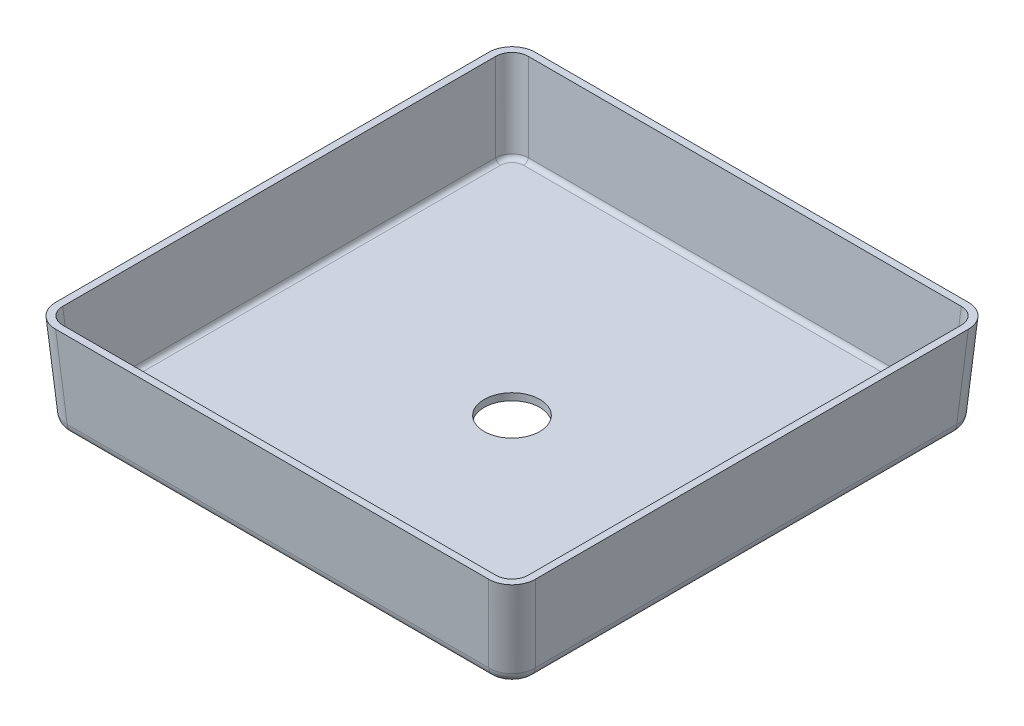
SolidWorks part; units mm, degrees
ref_plane "Alzado" through (0, 0, 0) normal (0, 0, 1) x (1, 0, 0)
ref_plane "Planta" through (0, 0, 0) normal (0, 1, 0) x (1, 0, 0)
ref_plane "Vista lateral" through (0, 0, 0) normal (1, 0, 0) x (0, 0, -1)
sketch "Croquis1" plane through (0, 0, 0) normal (0, 1, 0) x (1, 0, 0)
  line L1 (100, -100) -> (-100, -100)
  line L2 (100, -100) -> (100, 100)
  line L3 (100, 100) -> (-100, 100)
  line L4 (-100, -100) -> (-100, 100)
  line L5 (100, -100) -> (-100, 100) construction
  line L6 (100, 100) -> (-100, -100) construction
  point P0 (0, 0)
  dimension "D1" = 200
  dimension "D2" = 200
extrude "Extruir1" add sketch "Croquis1" along normal blind 40 draft 4 draft outward yes
fillet "Redondeo1" radius 10 4 edges at (-101.3985, 20, 101.3985) (-101.3985, 20, -101.3985) (101.3985, 20, 101.3985) (101.3985, 20, -101.3985)
fillet "Redondeo2" radius 5 8 edges at (97.0811, 0, 97.0811) (100, 0, 0) (97.0811, 0, -97.0811) (0, 0, -100) (-97.0811, 0, -97.0811) (-100, 0, 0) (-97.0811, 0, 97.0811) (0, 0, 100)
shell "Vaciado1" thickness 3 removed face at (0, 40, 0)
sketch "Croquis2" plane through (0, 3, 0) normal (0, 1, 0) x (1, 0, 0)
  circle A0 centre (0, 0) radius 11.9266
extrude "Extruir2" cut sketch "Croquis2" against normal through all
